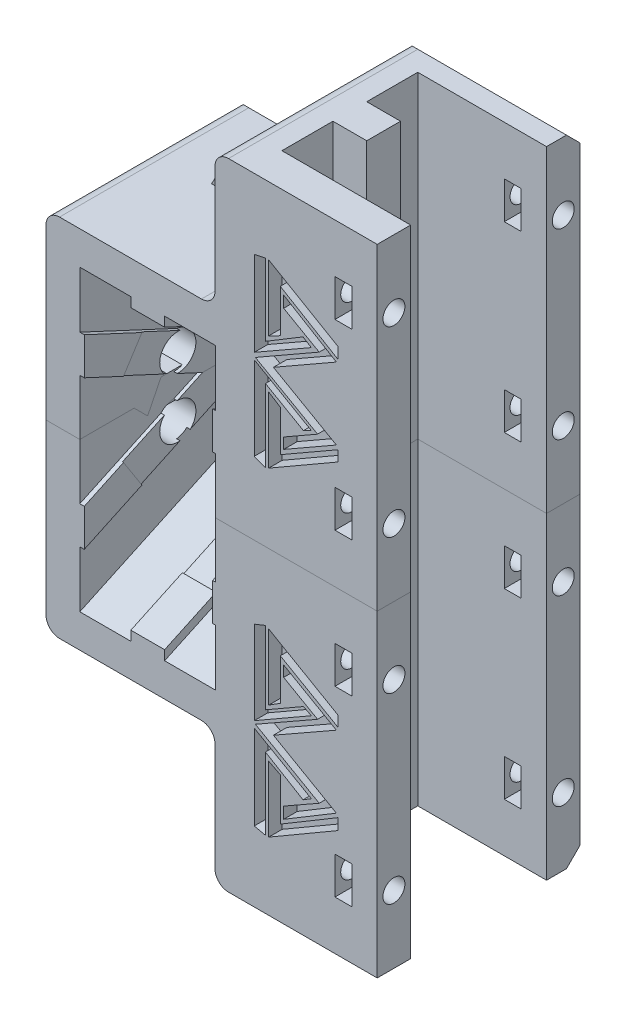
SolidWorks part; units mm, degrees
ref_plane "Front Plane" through (0, 0, 0) normal (0, 0, 1) x (1, 0, 0)
ref_plane "Top Plane" through (0, 0, 0) normal (0, 1, 0) x (1, 0, 0)
ref_plane "Right Plane" through (0, 0, 0) normal (1, 0, 0) x (0, 0, -1)
sketch "Sketch1" plane through (0, 0, 0) normal (0, 1, 0) x (1, 0, 0)
  line L1 (-15, -15) -> (15, -15)
  line L2 (-15, -15) -> (-15, 15)
  line L3 (-15, 15) -> (15, 15)
  line L4 (15, -15) -> (15, 15)
  line L5 (-15, -15) -> (15, 15) construction
  line L6 (-15, 15) -> (15, -15) construction
  point P0 (0, 0)
  dimension "D1" = 30
  dimension "D2" = 30
extrude "Boss-Extrude1" add sketch "Sketch1" along normal blind 50
sketch "Sketch2" plane through (0, 50, 0) normal (0, 1, 0) x (1, 0, 0)
  line L1 (-10.05, -10.05) -> (10.05, -10.05)
  line L2 (-10.05, -10.05) -> (-10.05, 10.05)
  line L3 (-10.05, 10.05) -> (10.05, 10.05)
  line L4 (10.05, -10.05) -> (10.05, 10.05)
  line L5 (-10.05, -10.05) -> (10.05, 10.05) construction
  line L6 (-10.05, 10.05) -> (10.05, -10.05) construction
  line L7 (-10.05, 0) -> (10.05, 0) construction
  line L8 (-10.05, 2.5) -> (-5.05, 2.5)
  line L9 (-5.05, 2.5) -> (-5.05, -2.5)
  line L10 (-5.05, -2.5) -> (-10.05, -2.5)
  point P0 (0, 0)
  dimension "D1" = 20.1
  dimension "D2" = 20.1
  dimension "D3" = 5
  dimension "D4" = 2.5
  dimension "D5" = 5
extrude "Cut-Extrude1" cut sketch "Sketch2" against normal through all contours L9 L10 L2 L1 L4 L3 L8
sketch "Sketch3" plane through (0, 50, 0) normal (0, 1, 0) x (1, 0, 0)
  line L0 (15, 15) -> (-15, 15) construction
  line L1 (9, 15) -> (15, 15)
  line L2 (9, 15) -> (9, -15)
  line L3 (9, -15) -> (15, -15)
  line L4 (15, 15) -> (15, -15)
  line L5 (-15, -15) -> (15, -15) construction
  dimension "D1" = 6
extrude "Cut-Extrude2" cut sketch "Sketch3" against normal through all
sketch "Sketch5" plane through (-15, 0, 0) normal (-1, 0, 0) x (0, 0, 1)
  line L1 (-15, 30) -> (15, 30)
  line L2 (-15, 30) -> (-15, 0)
  line L3 (-15, 0) -> (15, 0)
  line L4 (15, 30) -> (15, 0)
extrude "Boss-Extrude2" add sketch "Sketch5" along normal blind 25
sketch "Sketch6" plane through (-40, 0, 0) normal (-1, 0, 0) x (0, 0, 1)
  line L0 (-23.4514, 12.0698) -> (15, 30) construction
  line L1 (15, 0) -> (15, 30) construction
  dimension "D1" = 65
ref_plane "45 Angle plane" through (-40, 12.0698, -23.4514) normal (0, -0.4226, -0.9063) x (-1, 0, 0)
sketch "Sketch7" plane through (-40, 12.0698, -23.4514) normal (0, -0.4226, -0.9063) x (-1, 0, 0)
  line L0 (-49, -14.5107) -> (0, -14.5107) construction
  line L1 (-25.1, -24.5607) -> (-5, -24.5607)
  line L2 (-25.1, -24.5607) -> (-25.1, -4.4607)
  line L3 (-25.1, -4.4607) -> (-5, -4.4607)
  line L4 (-5, -24.5607) -> (-5, -4.4607)
  line L5 (-25.1, -24.5607) -> (-5, -4.4607) construction
  line L6 (-25.1, -4.4607) -> (-5, -24.5607) construction
  line L7 (0, -14.5107) -> (0, -27.1892) construction
  line L8 (-15.05, -4.4607) -> (-15.05, -24.5607) construction
  line L9 (-25.1, -14.5107) -> (-5, -14.5107)
  line L10 (-12.55, -4.4607) -> (-12.55, -9.4607)
  line L11 (-12.55, -9.4607) -> (-17.55, -9.4607)
  line L12 (-17.55, -9.4607) -> (-17.55, -4.4607)
  line L13 (-25.1, -12.0107) -> (-20.1, -12.0107)
  line L14 (-20.1, -12.0107) -> (-20.1, -17.0107)
  line L15 (-20.1, -17.0107) -> (-25.1, -17.0107)
  line L16 (-12.55, -24.5607) -> (-12.55, -19.5607)
  line L17 (-12.55, -19.5607) -> (-17.55, -19.5607)
  line L18 (-17.55, -19.5607) -> (-17.55, -24.5607)
  line L19 (-5, -12.0107) -> (-10, -12.0107)
  line L20 (-10, -12.0107) -> (-10, -17.0107)
  line L21 (-10, -17.0107) -> (-5, -17.0107)
  point P0 (-15.05, -14.5107)
  dimension "D1" = 20.1
  dimension "D2" = 20.1
  dimension "D3" = 5
  dimension "D4" = 5
  dimension "D5" = 2.5
  dimension "D6" = 5
  dimension "D7" = 5
  dimension "D8" = 5
  dimension "D9" = 2.5
extrude "45 degree extrusion cut" cut sketch "Sketch7" against normal through all contours L21 L20 L9 L14 L15 L2 L1 L18 L17 L16 L4 | L20 L19 L4 L3 L10 L11 L12 L2 L13 L14 L9
sketch "Sketch11" plane through (9, 0, 0) normal (1, 0, 0) x (0, 0, -1)
  line L0 (12.525, 50) -> (12.525, 40) construction
  line L1 (15, 50) -> (10.05, 50) construction
  line L2 (12.525, 0) -> (12.525, 13) construction
  line L3 (15, 0) -> (10.05, 0) construction
  line L4 (-12.525, 0) -> (-12.525, 13) construction
  line L5 (-10.05, 0) -> (-15, 0) construction
  line L6 (-12.525, 50) -> (-12.525, 40) construction
  line L7 (-10.05, 50) -> (-15, 50) construction
  circle A0 centre (-12.525, 40) radius 1.625
  circle A1 centre (12.525, 40) radius 1.625
  circle A2 centre (12.525, 13) radius 1.625
  circle A3 centre (-12.525, 13) radius 1.625
  dimension "D5" = 3.25
  dimension "D6" = 3.25
  dimension "D7" = 3.25
  dimension "D8" = 3.25
  dimension "D1" = 10
  dimension "D2" = 10
  dimension "D3" = 13
  dimension "D4" = 13
extrude "Cut-Extrude7" cut sketch "Sketch11" against normal blind 10
chamfer "Chamfer1" distance 2 angle 45 7 edges at (-5.45, 0, -15) (9, 25, -15) (-35, 0, -15) (-3, 50, -15) (-40, 15, -15)
fillet "Fillet1" radius 2 4 edges at (-15, 50, 1) (-40, 30, 1) (-40, 0, 1)
sketch "Sketch16" plane through (-40, 0, 0) normal (-1, 0, 0) x (0, 0, 1)
  line L0 (15, 13.9434) -> (-13, 0.8868) construction
  line L1 (15, 2) -> (15, 28) construction
  line L2 (-13, 28) -> (-13, 2) construction
  line L3 (-23.4514, 12.0698) -> (15, 30) construction
  circle A0 centre (1, 7.4151) radius 2.675
  dimension "D1" = 5.35
extrude "Cut-Extrude10" cut sketch "Sketch16" against normal blind 10
ref_plane "Plane1" through (-25, 0, 0) normal (-1, 0, 0) x (0, 0, 1)
sketch "Sketch18" plane through (-25, 0, 0) normal (-1, 0, 0) x (0, 0, 1)
  line L0 (14.8471, 13.729) -> (1, 7.4151) construction
  line L4 (9.9507, 7.3478) -> (5.6064, 14.1277)
  line L5 (9.9507, 7.3478) -> (-3.6064, 0.7025)
  line L6 (5.6064, 14.1277) -> (-7.9507, 7.4825)
  line L7 (-3.6064, 0.7025) -> (-7.9507, 7.4825)
  dimension "D1" = 8
  dimension "D2" = 15
  dimension "D3" = 7.5
  dimension "D4" = 4
extrude "Cut-Extrude11" cut sketch "Sketch18" against normal mid plane 19
fillet "Fillet2" radius 0.5 1 edges at (-24.95, 0, -3.0507)
fillet "Fillet3" radius 0.5 1 edges at (-24.95, 8.4172, 15)
sketch "Sketch19" plane through (0, 0, 15) normal (0, 0, 1) x (1, 0, 0)
  line L0 (-40, 2) -> (-40, 28) construction
  line L1 (-40, 3) -> (9, 3)
  line L2 (-40, 3) -> (-40, 0)
  line L3 (-40, 0) -> (9, 0)
  line L4 (9, 3) -> (9, 0)
  dimension "D1" = 3
extrude "Cut-Extrude12" cut sketch "Sketch19" against normal through all
sketch "Sketch20" plane through (0, 0, 15) normal (0, 0, 1) x (1, 0, 0)
  line L1 (-28.5785, 8.4284) -> (-21.8248, 8.4284)
  line L2 (-28.5785, 8.4284) -> (-28.5785, 2.1753)
  line L3 (-28.5785, 2.1753) -> (-21.8248, 2.1753)
  line L4 (-21.8248, 8.4284) -> (-21.8248, 2.1753)
extrude "Cut-Extrude13" cut sketch "Sketch20" against normal blind 15
sketch "Sketch21" plane through (-25, 0, 0) normal (-1, 0, 0) x (0, 0, 1)
  line L0 (-7.6246, 31.9083) -> (1.6243, 14.3185) construction
ref_plane "Plane2" through (-25, 31.9083, -7.6246) normal (0, 0.8851, -0.4654) x (1, 0, 0)
sketch "Sketch22" plane through (-25, 31.9083, -7.6246) normal (0, 0.8851, -0.4654) x (1, 0, 0)
  circle A0 centre (0.022, 0.0143) radius 2.65
  dimension "D1" = 5.3
extrude "Cut-Extrude14" cut sketch "Sketch22" against normal through all
sketch "Sketch23" plane through (-25, 31.9083, -7.6246) normal (0, 0.8851, -0.4654) x (1, 0, 0)
  circle A0 centre (0.022, 0.0143) radius 6
  dimension "D1" = 12
extrude "Cut-Extrude15" cut sketch "Sketch23" against normal blind 5 draft 23 draft outward yes
sketch "Sketch24" plane through (0, 10.3222, -4.8133) normal (0, -0.9063, 0.4226) x (1, 0, 0)
  line L0 (-27.45, 21.8616) -> (-27.45, 8.5079) construction
  line L1 (-27.45, 15.1847) -> (-22.45, 15.1847)
  line L2 (-27.45, 15.1847) -> (-27.45, 0.1847)
  line L3 (-27.45, 0.1847) -> (-22.45, 0.1847)
  line L4 (-22.45, 15.1847) -> (-22.45, 0.1847)
  line L5 (-22.45, 6.7563) -> (-22.45, -11.2398) construction
  dimension "D1" = 15
extrude "Cut-Extrude16" cut sketch "Sketch24" against normal blind 4
sketch "Sketch25" plane through (0, 3, 0) normal (0, -1, 0) x (1, 0, 0)
  line L0 (-40, -23.4514) -> (-40, 15) construction
  line L1 (-40, 6.9649) -> (-35, 6.9649)
  line L2 (-40, 6.9649) -> (-40, -5.1295)
  line L3 (-40, -5.1295) -> (-35, -5.1295)
  line L4 (-35, 6.9649) -> (-35, -5.1295)
  line L5 (-35, 15) -> (-35, -2.651) construction
extrude "Boss-Extrude3" add sketch "Sketch25" along normal blind 2
chamfer "Chamfer2" distance 2 angle 45 2 edges at (-37.5, 1, -5.1295) (-37.5, 1, 6.9649)
sketch "Sketch26" plane through (0, 0, 15) normal (0, 0, 1) x (1, 0, 0)
  line L0 (4, 50) -> (4, 40) construction
  line L1 (-13, 50) -> (9, 50) construction
  line L2 (4, 3) -> (4, 13) construction
  line L3 (9, 3) -> (-14.9, 3) construction
  line L4 (9, 3) -> (9, 50) construction
  line L6 (2.75, 37.25) -> (5.25, 37.25)
  line L7 (2.75, 37.25) -> (2.75, 42.75)
  line L8 (2.75, 42.75) -> (5.25, 42.75)
  line L9 (5.25, 37.25) -> (5.25, 42.75)
  line L10 (2.75, 37.25) -> (5.25, 42.75) construction
  line L11 (2.75, 42.75) -> (5.25, 37.25) construction
  line L12 (2.75, 10.25) -> (5.25, 10.25)
  line L13 (2.75, 10.25) -> (2.75, 15.75)
  line L14 (2.75, 15.75) -> (5.25, 15.75)
  line L15 (5.25, 10.25) -> (5.25, 15.75)
  line L16 (2.75, 10.25) -> (5.25, 15.75) construction
  line L17 (2.75, 15.75) -> (5.25, 10.25) construction
  dimension "D1" = 10
  dimension "D2" = 5
  dimension "D3" = 10
  dimension "D4" = 5
  dimension "D5" = 5.5
  dimension "D6" = 2.5
  dimension "D7" = 2.5
  dimension "D8" = 5.5
extrude "Cut-Extrude17" cut sketch "Sketch26" against normal through all
fillet "Fillet4" radius 0.5 3 edges at (-24.95, 5.5721, -15) (-32.5, 3, -14.482) (-17.4, 3, -14.482)
sketch "Mobious Logo" plane through (0, 0, 15) normal (0, 0, 1) x (-1, 0, 0)
  line L0 (-3.2109, -32.3487) -> (-3.2109, -34.0037)
  line L1 (-3.2109, -34.0037) -> (7.0562, -39.9788)
  line L2 (7.0562, -39.9788) -> (7.0562, -30.2448)
  line L3 (7.0562, -30.2448) -> (5.3383, -31.1222)
  line L4 (5.3383, -31.1222) -> (5.3383, -37.4541)
  line L5 (5.3383, -37.4541) -> (-3.2109, -32.3487)
  line L6 (1.9787, -32.6572) -> (0.7445, -31.8998)
  line L7 (0.7445, -31.8998) -> (9.1881, -27.0749)
  line L8 (9.1881, -27.0749) -> (9.1881, -39.6141)
  line L9 (9.1881, -39.6141) -> (7.533, -39.9851)
  line L10 (7.533, -39.9851) -> (7.533, -29.3079)
  line L11 (7.533, -29.3079) -> (1.9787, -32.6572)
  line L12 (4.84, -36.5845) -> (-2.9584, -31.8998)
  line L13 (-2.9584, -31.8998) -> (6.3555, -26.5699)
  line L14 (6.3555, -26.5699) -> (-2.9584, -21.2681)
  line L15 (-2.9584, -21.2681) -> (4.84, -16.8055)
  line L16 (4.84, -16.8055) -> (4.84, -18.4002)
  line L17 (4.84, -18.4002) -> (-0.1715, -21.2681)
  line L18 (-0.1715, -21.2681) -> (9.0195, -26.5)
  line L19 (9.0195, -26.5) -> (-0.4166, -31.8998)
  line L20 (-0.4166, -31.8998) -> (4.84, -34.8921)
  line L21 (4.84, -34.8921) -> (4.84, -36.5845)
  line L22 (-3.2109, -20.7912) -> (-3.2109, -19.2203)
  line L23 (-3.2109, -19.2203) -> (7.0562, -13.3014)
  line L24 (7.0562, -13.3014) -> (7.0562, -23.0634)
  line L25 (7.0562, -23.0634) -> (5.3383, -21.9694)
  line L26 (5.3383, -21.9694) -> (5.3383, -15.8821)
  line L27 (5.3383, -15.8821) -> (-3.2109, -20.7912)
  line L28 (0.7445, -21.2681) -> (9.1881, -26.1211)
  line L29 (9.1881, -26.1211) -> (9.1881, -13.7502)
  line L30 (9.1881, -13.7502) -> (7.533, -13.0939)
  line L31 (7.533, -13.0939) -> (7.533, -23.905)
  line L32 (7.533, -23.905) -> (1.9157, -20.6765)
  line L33 (1.9157, -20.6765) -> (0.7445, -21.2681)
  line L34 (-9, -26.5) -> (14.8874, -26.5) construction
  line L35 (-9, -3) -> (-9, -50) construction
extrude "Cut-Extrude18" cut sketch "Mobious Logo" against normal blind 2
chamfer "Chamfer3" distance 2 angle 45 1 edges at (-24.978, 30, -11.2539)
fillet "Fillet5" radius 0.2 1 edges at (-24.978, 30, -12.7348)
sketch "Sketch29" plane through (-40, 12.0698, -23.4514) normal (0, -0.4226, -0.9063) x (-1, 0, 0)
  line L0 (-11.6431, -11.1008) -> (-5.6637, -11.1008)
  line L1 (-24.6636, -11.1008) -> (-19.2744, -11.1008)
  line L2 (-24.6636, -11.1008) -> (-24.6636, -19.3624)
  line L3 (-24.6636, -19.3624) -> (-5.6637, -19.3624)
  line L4 (-5.6637, -11.1008) -> (-5.6637, -19.3624)
  line L5 (-19.2744, -5.7472) -> (-11.6431, -5.7472)
  line L6 (-19.2744, -5.7472) -> (-19.2744, -11.1008)
  line L8 (-11.6431, -5.7472) -> (-11.6431, -11.1008)
extrude "Cut-Extrude21" cut sketch "Sketch29" against normal through all
mirror "Mirror1" about plane through (-40, 3, -15) normal (0, 1, 0) of bodies 124
